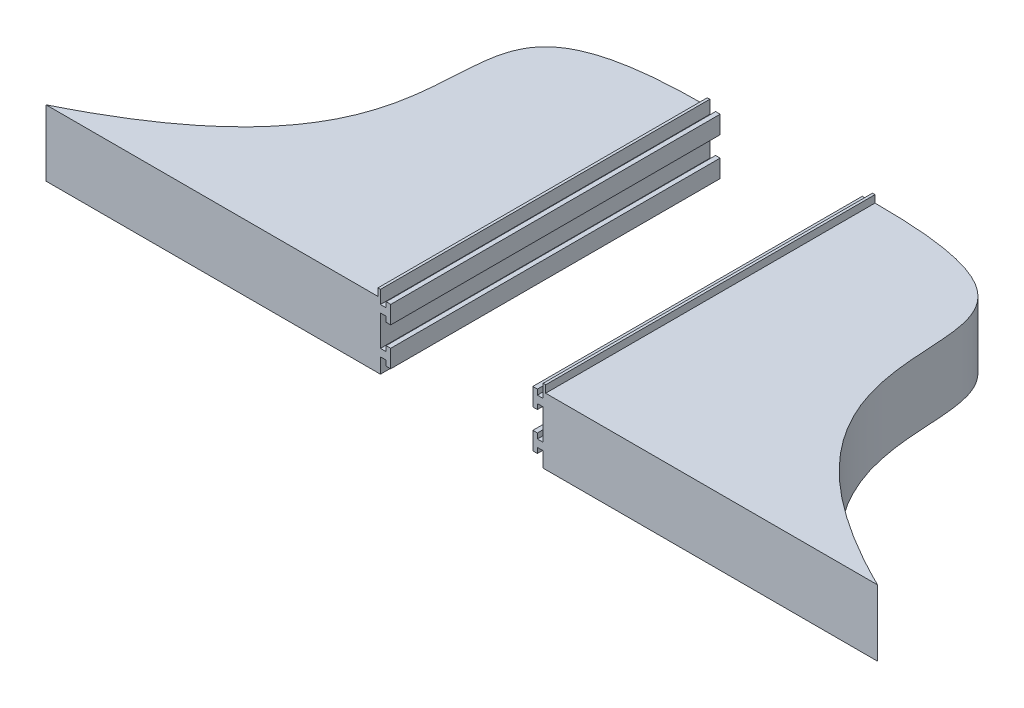
SolidWorks part; units mm, degrees
material "PLA"
ref_plane "Front Plane" through (0, 0, 0) normal (0, 0, 1) x (1, 0, 0)
ref_plane "Top Plane" through (0, 0, 0) normal (0, 1, 0) x (1, 0, 0)
ref_plane "Right Plane" through (0, 0, 0) normal (1, 0, 0) x (0, 0, -1)
ref_plane "Rail start" through (0, 0, -130) normal (0, 0, 1) x (1, 0, 0)
sketch "Sketch1" plane through (0, 0, -130) normal (0, 0, 1) x (1, 0, 0)
  line L440 (-32.1, -15.0497) -> (-32.1, -21)
  line L441 (-29.8428, -15.0497) -> (-32.1, -15.0497)
  line L442 (-29.8428, -17.1189) -> (-29.8428, -15.0497)
  line L443 (-28.0428, -17.1189) -> (-29.8428, -17.1189)
  line L444 (-28.0428, -10.1) -> (-28.0428, -17.1189)
  line L445 (-29.8428, -10.1) -> (-28.0428, -10.1)
  line L446 (-29.8428, -12.1692) -> (-29.8428, -10.1)
  line L447 (-32.1, -12.1692) -> (-29.8428, -12.1692)
  line L448 (-32.1, -0.0497) -> (-32.1, -12.1692)
  line L449 (-29.8428, -0.0497) -> (-32.1, -0.0497)
  line L450 (-29.8428, -2.1189) -> (-29.8428, -0.0497)
  line L451 (-28.0428, -2.1189) -> (-29.8428, -2.1189)
  line L452 (-28.0428, 4.9) -> (-28.0428, -2.1189)
  line L453 (-29.8428, 4.9) -> (-28.0428, 4.9)
  line L454 (-29.8428, 2.8308) -> (-29.8428, 4.9)
  line L455 (-32.1, 2.8308) -> (-29.8428, 2.8308)
  line L456 (-32.1, 8) -> (-32.1, 2.8308)
  line L457 (-32.1, -15.0497) -> (-32.1, -21)
  line L458 (-29.8428, -15.0497) -> (-32.1, -15.0497)
  line L459 (-29.8428, -17.1189) -> (-29.8428, -15.0497)
  line L460 (-28.0428, -17.1189) -> (-29.8428, -17.1189)
  line L461 (-28.0428, -10.1) -> (-28.0428, -17.1189)
  line L462 (-29.8428, -10.1) -> (-28.0428, -10.1)
  line L463 (-29.8428, -12.1692) -> (-29.8428, -10.1)
  line L464 (-32.1, -12.1692) -> (-29.8428, -12.1692)
  line L465 (-32.1, -0.0497) -> (-32.1, -12.1692)
  line L466 (-29.8428, -0.0497) -> (-32.1, -0.0497)
  line L467 (-29.8428, -2.1189) -> (-29.8428, -0.0497)
  line L468 (-28.0428, -2.1189) -> (-29.8428, -2.1189)
  line L469 (-28.0428, 4.9) -> (-28.0428, -2.1189)
  line L470 (-29.8428, 4.9) -> (-28.0428, 4.9)
  line L471 (-29.8428, 2.8308) -> (-29.8428, 4.9)
  line L472 (-32.1, 2.8308) -> (-29.8428, 2.8308)
  line L473 (-32.1, 8) -> (-32.1, 2.8308)
  line L474 (-32.1, -21) -> (-33.1, -21)
  line L475 (-33.1, -21) -> (-33.1, 8)
  line L476 (-33.1, 8) -> (-32.1, 8)
  dimension "D1" = 0.1
extrude "Boss-Extrude1" add sketch "Sketch1" along normal up to surface (130 mm away)
sketch "Sketch2" plane through (75.2969, -0.8945, -218.7008) normal (0, 1, 0) x (1, 0, 0)
  line L0 (-108.3969, -88.7008) -> (-108.3969, -218.7008)
  line L2 (-239.3767, -218.7008) -> (-108.3969, -218.7008)
  line L4 (-108.3969, -218.7008) -> (-108.3969, -88.7008) construction
  line L5 (-107.3969, -218.7008) -> (-107.3969, -88.7008) construction
  line L9 (-108.3969, -88.7008) -> (-226.6247, -88.7008) construction
  line L10 (-226.6247, -88.7008) -> (-107.3969, -153.7008) construction
  line L11 (-107.3969, -153.7008) -> (-239.3767, -218.7008) construction
  line L15 (-108.3969, -218.7008) -> (-108.3969, -88.7008) construction
  spline S0 degree 3 poles (-108.3969, -88.7008) (-226.6247, -88.7008) (-107.3969, -153.7008) (-239.3767, -218.7008) knots 0 0 0 0 1 1 1 1
  point P2 (0, 0)
  point P3 (0, 0)
  point P5 (-108.3969, -167.0908)
  point P6 (-108.3969, -157.0329)
  point P9 (-108.3969, -101.9477)
  point P10 (-108.3969, -88.7008)
  point P11 (-108.3969, -167.0908)
  point P12 (-214.4004, -88.7008)
  point P13 (-167.4688, -121.0809)
  point P16 (0, 0)
  point P17 (0, 0)
  point P18 (0, 0)
  point P19 (-234.2034, -167.0908)
  point P20 (-250.9426, -167.0908)
  point P21 (-203.1964, -167.0908)
  point P22 (-239.3767, -167.0908)
  point P23 (-161.4688, -120.7682)
  point P24 (-226.6247, -88.7008)
  point P25 (-108.3969, -167.0908)
  point P26 (-108.3969, -218.7008)
  point P27 (-107.3969, -153.7008)
extrude "Boss-Extrude2" add sketch "Sketch2" along normal blind 6 and the other way up to surface (20.1055 mm away) other way up to face at (-32.6, -21, -65)
mirror "Mirror1" about plane through (0, 0, 0) normal (1, 0, 0) of bodies 102
